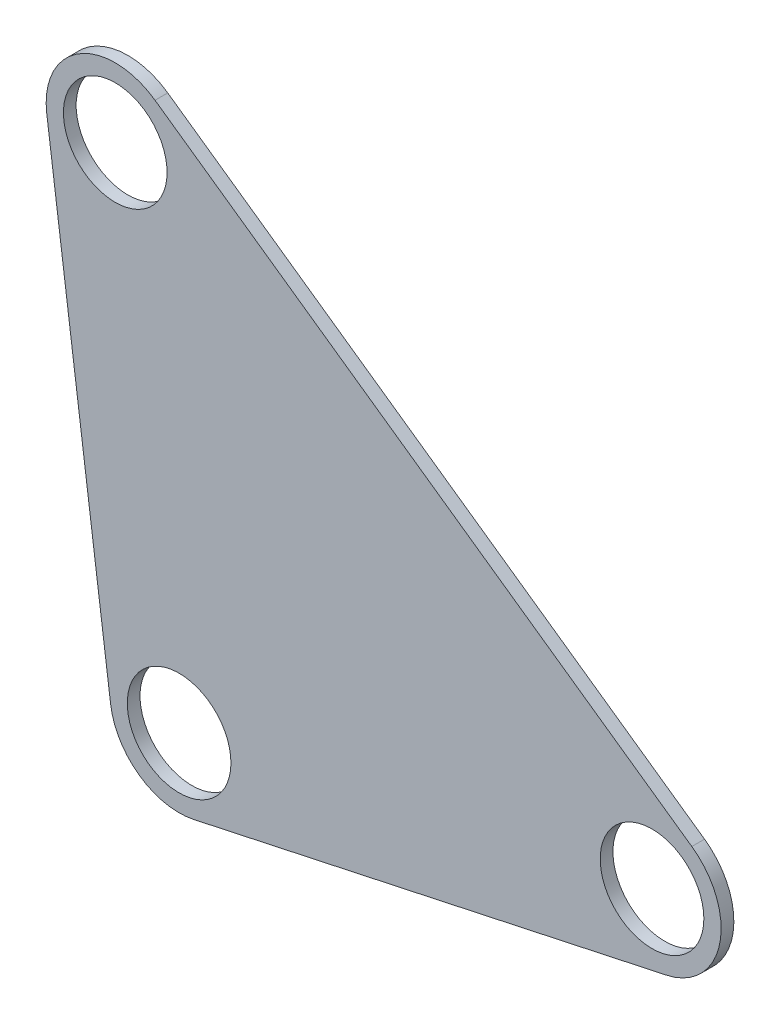
SolidWorks part; units mm, degrees
ref_plane "Plan de face" through (0, 0, 0) normal (0, 0, 1) x (1, 0, 0)
ref_plane "Plan de dessus" through (0, 0, 0) normal (0, 1, 0) x (1, 0, 0)
ref_plane "Plan de droite" through (0, 0, 0) normal (1, 0, 0) x (0, 0, -1)
sketch "Esquisse1" plane through (0, 0, 0) normal (0, 0, 1) x (1, 0, 0)
  line L2 (32.6051, -9.781) -> (59.9807, -3.9008)
  line L4 (27.8001, -6.3983) -> (24.1033, 21.3566)
  line L8 (61.4433, 3.2808) -> (30.3709, 25.1555)
  circle A6 centre (28.0683, 21.8847) radius 3
  circle A7 centre (31.7651, -5.8702) radius 3
  circle A8 centre (59.1407, 0.01) radius 3
  arc A9 (30.3709, 25.1555) -> (24.1033, 21.3566) centre (28.0683, 21.8847) ccw
  arc A10 (59.9807, -3.9008) -> (61.4433, 3.2808) centre (59.1407, 0.01) ccw
  arc A11 (32.6051, -9.781) -> (27.8001, -6.3983) centre (31.7651, -5.8702) cw
  point P4 (45.4529, -2.9301)
  point P9 (29.9167, 8.0073)
  point P17 (43.6045, 10.9473)
  dimension "D1" = 6
  dimension "D2" = 6
  dimension "D3" = 6
base flange "Tôle de base pliée1" sketch "Esquisse1" thickness 0.7366 reverse thickness direction no parameters "D1"=0.7366
sketch "Lignes de pliage1" [suppressed] plane through (0, 0, 0) normal (0, 1, 0) x (1, 0, 0)
sketch "Cube de visualisation1" [suppressed] plane through (0, 0, 0) normal (0, 1, 0) x (1, 0, 0)
sheet metal parameters "Tôlerie1" thickness 0.7366 parameters "D1"=0.7366
flat pattern "Etat déplié1" [suppressed]
sketch "Lignes de pliage2" plane through (0, 0, 0) normal (0, 1, 0) x (1, 0, 0)
sketch3d "Cube de visualisation2" [suppressed]
  line L0 (27.4078, 35.9332, 0) -> (32.1609, 0.2484, 0) construction
  line L1 (-8.1899, 31.1917, 0) -> (-3.4369, -4.4931, 0) construction
  line L2 (27.4078, 35.9332, 0) -> (-8.1899, 31.1917, 0) construction
  line L3 (32.1609, 0.2484, 0) -> (-3.4369, -4.4931, 0) construction
